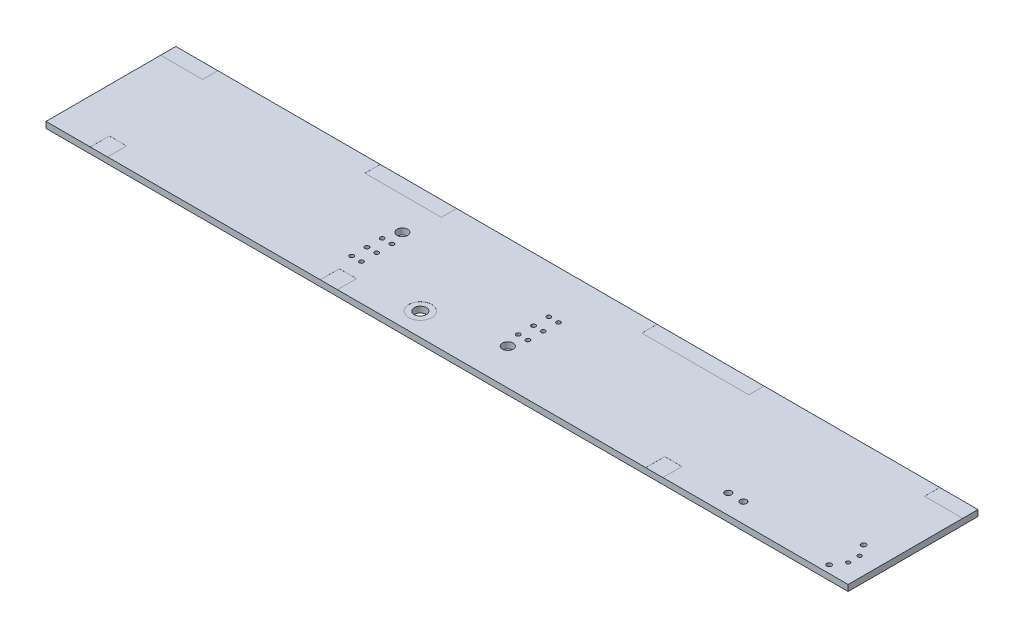
SolidWorks part; units mm, degrees
ref_plane "Plan de face" through (0, 0, 0) normal (0, 0, 1) x (1, 0, 0)
ref_plane "Plan de dessus" through (0, 0, 0) normal (0, 1, 0) x (1, 0, 0)
ref_plane "Plan de droite" through (0, 0, 0) normal (1, 0, 0) x (0, 0, -1)
sketch "Esquisse1" plane through (0, 0, 0) normal (0, 0, 1) x (1, 0, 0)
  line L1 (97.4067, -122.71) -> (-112.5933, -122.71)
  line L2 (-112.5933, -122.71) -> (-112.5933, -121.11)
  line L3 (97.4067, -121.11) -> (-112.5933, -121.11)
  line L5 (97.4067, -122.71) -> (97.4067, -121.11)
  dimension "D1" = 1.6
  dimension "D2" = 210
extrude "Board " add sketch "Esquisse1" along normal blind 34
sketch "Sketch1" plane through (0, -122.71, 0) normal (0, 1, 0) x (1, 0, 0)
  line L0 (-40.7933, -5.9874) -> (-40.7933, -30.8472) construction
  line L1 (-1.1933, -30.8472) -> (-1.1933, -4.7686) construction
  line L3 (-112.5933, -34) -> (-112.5933, 0) construction
  line L4 (-42.0633, -16.5) -> (-39.5233, -16.5) construction
  line L5 (-112.5933, 0) -> (97.4067, 0) construction
  circle A0 centre (-39.5233, -16.5) radius 0.55
  circle A1 centre (-42.0633, -16.5) radius 0.55
  circle A2 centre (-42.0633, -20.5) radius 0.55
  circle A3 centre (-42.0633, -24.5) radius 0.55
  circle A4 centre (-40.7933, -12.5) radius 1.4
  circle A5 centre (-39.5233, -20.5) radius 0.55
  circle A6 centre (-39.5233, -24.5) radius 0.55
  circle A7 centre (-2.4633, -20.5) radius 0.55
  circle A8 centre (0.0767, -20.5) radius 0.55
  circle A9 centre (-2.4633, -16.5) radius 0.55
  circle A10 centre (0.0767, -16.5) radius 0.55
  circle A11 centre (-2.4633, -12.5) radius 0.55
  circle A12 centre (0.0767, -12.5) radius 0.55
  circle A13 centre (-1.1933, -24.5) radius 1.4
  dimension "D1" = 2.54
  dimension "D2" = 1.1
  dimension "D7" = 4
  dimension "D8" = 4
  dimension "D9" = 2.8
  dimension "D11" = 2.54
  dimension "D12" = 2.54
  dimension "D14" = 4
  dimension "D15" = 2.8
  dimension "D5" = 71.8
  dimension "D6" = 16.5
  dimension "D10" = 39.6
  dimension "D3" = 2
  dimension "D4" = 3
  dimension "D13" = 3
extrude "Removeable Batt Con Holes" cut sketch "Sketch1" along normal through all
sketch "Sketch2" plane through (0, -122.71, 0) normal (0, -1, 0) x (1, 0, 0)
  line L1 (-112.5933, 34) -> (97.4067, 34) construction
  line L2 (97.4067, 34) -> (97.4067, 0) construction
  circle A0 centre (92.4067, 29) radius 0.51
  circle A1 centre (92.4067, 26) radius 0.51
  circle A2 centre (90.4467, 32) radius 0.635
  circle A3 centre (90.4467, 23) radius 0.635
  dimension "D2" = 1.02
  dimension "D3" = 1.96
  dimension "D4" = 5
  dimension "D5" = 1.27
  dimension "D6" = 3
  dimension "D8" = 5
  dimension "D1" = 2
  dimension "D7" = 2
extrude "DC Out Conn holes" cut sketch "Sketch2" against normal through all
sketch "Sketch3" plane through (0, -122.71, 0) normal (0, -1, 0) x (1, 0, 0)
  line L0 (-112.5933, 34) -> (97.4067, 34) construction
  line L2 (97.4067, 34) -> (97.4067, 0) construction
  circle A0 centre (64.9067, 28.92) radius 0.85
  circle A1 centre (60.9467, 28.92) radius 0.85
  dimension "D1" = 1.7
  dimension "D3" = 5.08
  dimension "D5" = 3.96
  dimension "D4" = 32.5
  dimension "D2" = 2
extrude "Charger conn holes" cut sketch "Sketch3" against normal through all
sketch "Sketch4" plane through (0, -121.11, 0) normal (0, 1, 0) x (1, 0, 0)
  line L0 (-112.5933, -34) -> (-112.5933, 0) construction
  line L1 (-112.5933, -34) -> (97.4067, -34) construction
  circle A0 centre (-20.5933, -28) radius 1.59
  dimension "D1" = 3.18
  dimension "D3" = 6
  dimension "D2" = 92
extrude "Cut-Extrude1" cut sketch "Sketch4" against normal through all
sketch "Sketch5" plane through (0, -121.11, 0) normal (0, 1, 0) x (1, 0, 0)
  line L0 (97.4067, 0) -> (-112.5933, 0) construction
  line L1 (97.4067, 0) -> (87.4067, 0)
  line L2 (97.4067, 0) -> (97.4067, -4)
  line L3 (97.4067, -4) -> (87.4067, -4)
  line L4 (87.4067, 0) -> (87.4067, -4)
  line L5 (41.4067, 0) -> (13.4067, 0)
  line L6 (41.4067, 0) -> (41.4067, -4)
  line L7 (41.4067, -4) -> (13.4067, -4)
  line L8 (13.4067, 0) -> (13.4067, -4)
  line L9 (-112.5933, -34) -> (-112.5933, 0) construction
  line L10 (-39.0933, 0) -> (-59.0933, 0)
  line L11 (-39.0933, 0) -> (-39.0933, -4)
  line L12 (-39.0933, -4) -> (-59.0933, -4)
  line L13 (-59.0933, 0) -> (-59.0933, -4)
  line L14 (-101.5933, 0) -> (-112.5933, 0)
  line L15 (-101.5933, 0) -> (-101.5933, -4)
  line L16 (-101.5933, -4) -> (-112.5933, -4)
  line L17 (-112.5933, 0) -> (-112.5933, -4)
  line L18 (97.4067, -34) -> (97.4067, 0) construction
  line L19 (97.4067, -34) -> (-112.5933, -34) construction
  line L20 (-100.9933, -34) -> (-96.4933, -34)
  line L21 (-100.9933, -34) -> (-100.9933, -29)
  line L22 (-100.9933, -29) -> (-96.4933, -29)
  line L23 (-96.4933, -34) -> (-96.4933, -29)
  line L25 (-40.7933, -34) -> (-36.2933, -34)
  line L26 (-40.7933, -34) -> (-40.7933, -29)
  line L27 (-40.7933, -29) -> (-36.2933, -29)
  line L28 (-36.2933, -34) -> (-36.2933, -29)
  line L29 (44.4067, -34) -> (48.9067, -34)
  line L30 (44.4067, -34) -> (44.4067, -29)
  line L31 (44.4067, -29) -> (48.9067, -29)
  line L32 (48.9067, -34) -> (48.9067, -29)
  circle A0 centre (-20.5933, -28) radius 3
  dimension "D20" = 6
  dimension "D1" = 10
  dimension "D2" = 4
  dimension "D3" = 11
  dimension "D4" = 4
  dimension "D5" = 4
  dimension "D6" = 20
  dimension "D7" = 53.5
  dimension "D8" = 28
  dimension "D9" = 4
  dimension "D10" = 56
  dimension "D11" = 4.5
  dimension "D12" = 5
  dimension "D13" = 11.6
  dimension "D14" = 71.8
  dimension "D15" = 4.5
  dimension "D16" = 5
  dimension "D17" = 5
  dimension "D18" = 4.5
  dimension "D19" = 48.5
extrude "Cut-Extrude2" cut sketch "Sketch5" against normal blind 0.01
extrude "Cut-Extrude3" cut sketch "Sketch5<2>" along normal blind 0.01 from surface starting at face at (-22.1833, -122.71, 28)
sketch "Sketch5<2>" plane through (0, -121.11, 0) normal (0, 1, 0) x (1, 0, 0) same geometry as "Sketch5"
sketch "Sketch6" plane through (0, -122.71, 0) normal (0, -1, 0) x (1, 0, 0)
  line L0 (57.4067, 34) -> (57.4067, 15.5)
  line L1 (97.4067, 34) -> (97.4067, 4) construction
  line L2 (-42.0633, 24.5) -> (-39.5233, 24.5) construction
  line L3 (-44.7933, 27.5) -> (-36.7933, 27.5)
  line L4 (-44.7933, 27.5) -> (-44.7933, 9.5)
  line L5 (-44.7933, 9.5) -> (-36.7933, 9.5)
  line L6 (-36.7933, 27.5) -> (-36.7933, 9.5)
  line L7 (-5.1933, 27.5) -> (2.8067, 27.5)
  line L8 (-5.1933, 27.5) -> (-5.1933, 9.5)
  line L9 (-5.1933, 9.5) -> (2.8067, 9.5)
  line L10 (2.8067, 27.5) -> (2.8067, 9.5)
  line L11 (-40.7933, 24.5) -> (-40.7933, 12.5) construction
  line L12 (-2.4633, 12.5) -> (0.0767, 12.5) construction
  line L13 (-1.1933, 12.5) -> (-1.1933, 24.5) construction
  line L14 (58.9067, 5.5) -> (64.4067, 0)
  line L15 (41.4067, 0) -> (87.4067, 0) construction
  line L16 (57.4067, 15.5) -> (58.9067, 15.5)
  line L17 (58.9067, 15.5) -> (58.9067, 5.5)
  line L28 (44.4067, 29) -> (44.4067, 34)
  line L29 (44.4067, 34) -> (-36.2933, 34)
  line L30 (-36.2933, 34) -> (-36.2933, 29)
  line L31 (-36.2933, 29) -> (-40.7933, 29)
  line L32 (-40.7933, 29) -> (-40.7933, 34)
  line L33 (-40.7933, 34) -> (-96.4933, 34)
  line L34 (-96.4933, 34) -> (-96.4933, 29)
  line L35 (-96.4933, 29) -> (-100.9933, 29)
  line L36 (-100.9933, 29) -> (-100.9933, 34)
  line L37 (-100.9933, 34) -> (-112.5933, 34)
  line L38 (-112.5933, 34) -> (-112.5933, 4)
  line L39 (-112.5933, 4) -> (-101.5933, 4)
  line L40 (-101.5933, 4) -> (-101.5933, 0)
  line L41 (-101.5933, 0) -> (-59.0933, 0)
  line L42 (-59.0933, 0) -> (-59.0933, 4)
  line L43 (-59.0933, 4) -> (-39.0933, 4)
  line L44 (-39.0933, 4) -> (-39.0933, 0)
  line L45 (-39.0933, 0) -> (13.4067, 0)
  line L46 (13.4067, 0) -> (13.4067, 4)
  line L47 (13.4067, 4) -> (41.4067, 4)
  line L48 (41.4067, 4) -> (41.4067, 0)
  line L49 (41.4067, 0) -> (87.4067, 0)
  line L50 (87.4067, 0) -> (87.4067, 4)
  line L51 (87.4067, 4) -> (97.4067, 4)
  line L52 (97.4067, 4) -> (97.4067, 34)
  line L53 (97.4067, 34) -> (48.9067, 34)
  line L54 (48.9067, 34) -> (48.9067, 29)
  line L55 (48.9067, 29) -> (44.4067, 29)
  line L56 (44.4067, 29) -> (44.4067, 34)
  line L57 (44.4067, 34) -> (-36.2933, 34)
  line L58 (-36.2933, 34) -> (-36.2933, 29)
  line L59 (-36.2933, 29) -> (-40.7933, 29)
  line L60 (-40.7933, 29) -> (-40.7933, 34)
  line L61 (-40.7933, 34) -> (-96.4933, 34)
  line L62 (-96.4933, 34) -> (-96.4933, 29)
  line L63 (-96.4933, 29) -> (-100.9933, 29)
  line L64 (-100.9933, 29) -> (-100.9933, 34)
  line L65 (-100.9933, 34) -> (-112.5933, 34)
  line L66 (-112.5933, 34) -> (-112.5933, 4)
  line L67 (-112.5933, 4) -> (-101.5933, 4)
  line L68 (-101.5933, 4) -> (-101.5933, 0)
  line L69 (-101.5933, 0) -> (-59.0933, 0)
  line L70 (-59.0933, 0) -> (-59.0933, 4)
  line L71 (-59.0933, 4) -> (-39.0933, 4)
  line L72 (-39.0933, 4) -> (-39.0933, 0)
  line L73 (-39.0933, 0) -> (13.4067, 0)
  line L74 (13.4067, 0) -> (13.4067, 4)
  line L75 (13.4067, 4) -> (41.4067, 4)
  line L76 (41.4067, 4) -> (41.4067, 0)
  line L77 (41.4067, 0) -> (64.4067, 0)
  line L81 (57.4067, 34) -> (48.9067, 34)
  line L82 (48.9067, 34) -> (48.9067, 29)
  line L83 (48.9067, 29) -> (44.4067, 29)
  dimension "D2" = 40
  dimension "D3" = 18
  dimension "D4" = 18
  dimension "D5" = 9.5
  dimension "D6" = 9.5
  dimension "D7" = 8
  dimension "D8" = 8
  dimension "D9" = 8
  dimension "D10" = 8
  dimension "D11" = 45
  dimension "D12" = 7
  dimension "D13" = 1.5
  dimension "D14" = 15.5
  dimension "D1" = 0
extrude "Cut-Extrude4" cut sketch "Sketch6" against normal blind 0.001
sketch "Sketch7" plane through (0, -122.71, 0) normal (0, -1, 0) x (1, 0, 0)
  line L0 (97.4067, 34) -> (97.4067, 4) construction
  line L1 (64.4067, 0) -> (87.4067, 0) construction
  circle A0 centre (64.4067, 17.5) radius 4
  circle A1 centre (64.4067, 8) radius 4
  dimension "D1" = 8
  dimension "D3" = 8
  dimension "D4" = 9.5
  dimension "D2" = 33
extrude "Boss-Extrude1" add sketch "Sketch7" along normal blind 10.2
sketch "Sketch8" plane through (0, -122.71, 0) normal (0, -1, 0) x (1, 0, 0)
  line L0 (82.3743, 7.884) -> (87.6067, 7.884)
  line L1 (87.6067, 7.884) -> (87.6067, 6.354)
  line L2 (82.3743, 6.354) -> (82.3743, 7.884)
  line L3 (97.4067, 4) -> (97.4067, 0) construction
  line L4 (97.4067, 0) -> (87.4067, 0) construction
  arc A0 (87.6067, 6.354) -> (82.3743, 6.354) centre (84.9905, 6.354) cw
  dimension "D2" = 1.53
  dimension "D1" = 5.2324
  dimension "D3" = 9.8
  dimension "D4" = 7.884
extrude "Boss-Extrude2" add sketch "Sketch8" along normal blind 3
